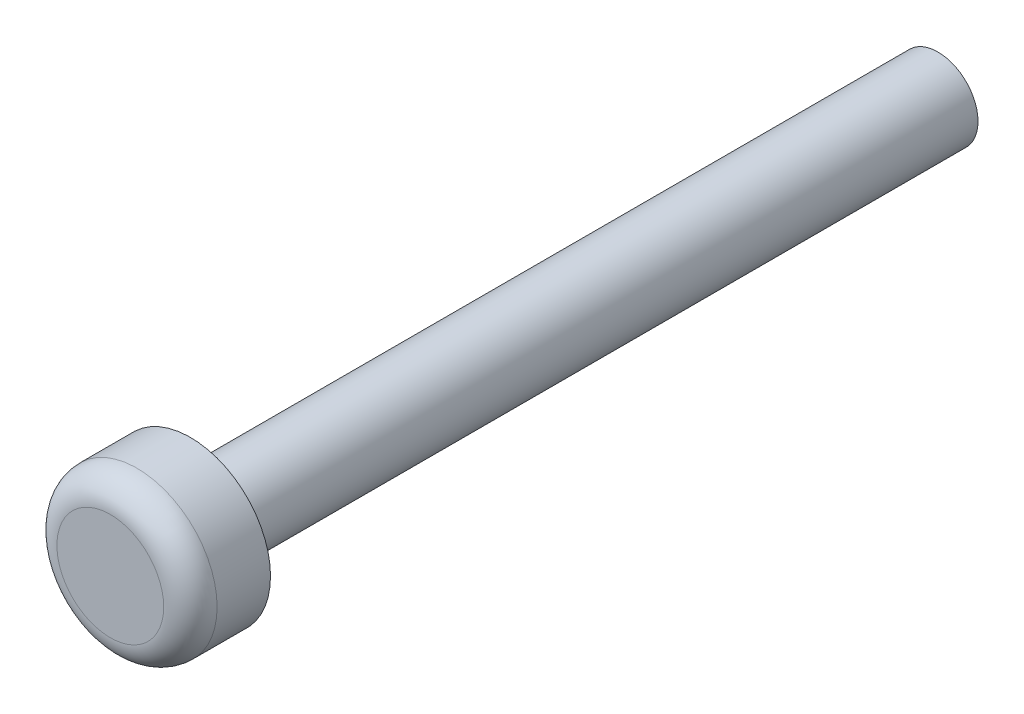
SolidWorks part; units mm, degrees
ref_plane "Front Plane" through (0, 0, 0) normal (0, 0, 1) x (1, 0, 0)
ref_plane "Top Plane" through (0, 0, 0) normal (0, 1, 0) x (1, 0, 0)
ref_plane "Right Plane" through (0, 0, 0) normal (1, 0, 0) x (0, 0, -1)
sketch "Sketch1" plane through (0, 0, 0) normal (0, 0, 1) x (1, 0, 0)
  circle A1 centre (0, 0) radius 1.5
extrude "Boss-Extrude1" add sketch "Sketch1" against normal blind 28
sketch "Sketch2" plane through (0, 0, 0) normal (0, 0, 1) x (1, 0, 0)
  circle A0 centre (0, 0) radius 3
extrude "Boss-Extrude2" add sketch "Sketch2" along normal blind 3
fillet "Fillet1" radius 1 1 edges at (3, 0, 3)
